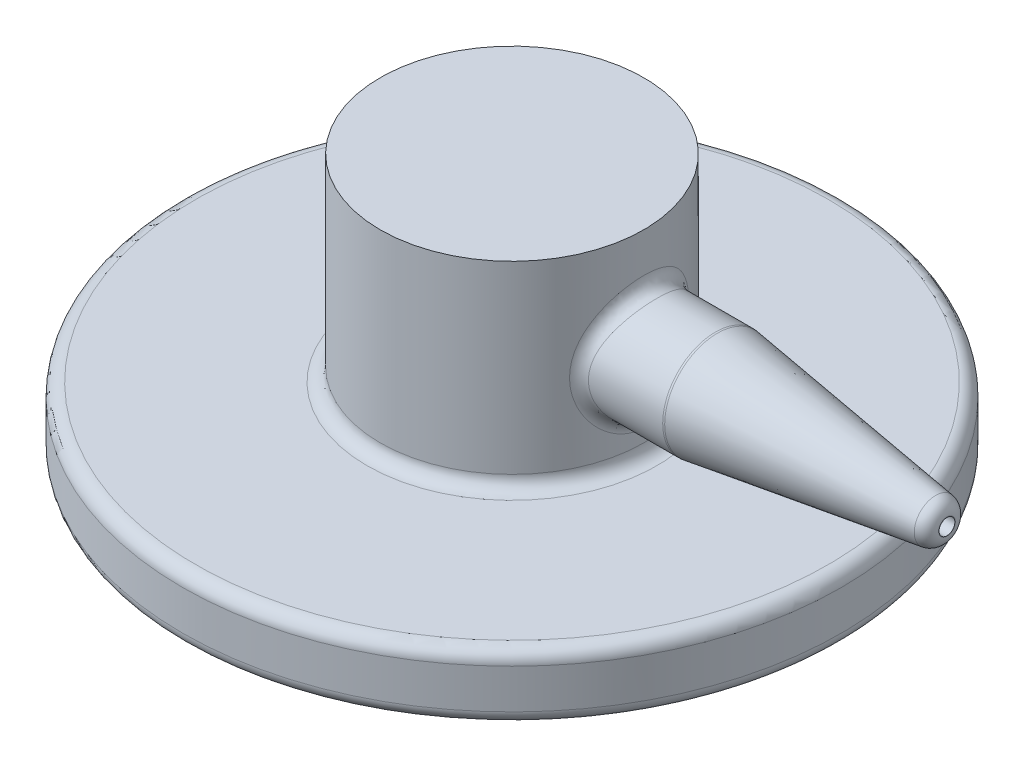
SolidWorks part; units mm, degrees
ref_plane "Ön Düzlem" through (0, 0, 0) normal (0, 0, 1) x (1, 0, 0)
ref_plane "Üst Düzlem" through (0, 0, 0) normal (0, 1, 0) x (1, 0, 0)
ref_plane "Sağ Düzlem" through (0, 0, 0) normal (1, 0, 0) x (0, 0, -1)
sketch "Sketch1" plane through (0, 0, 0) normal (0, 0, 1) x (1, 0, 0)
  line L0 (0, 20) -> (0, 0)
  line L8 (10, 20) -> (10, 5)
  line L9 (10, 5) -> (25, 5)
  line L10 (25, 5) -> (25, 0)
  line L11 (25, 0) -> (0, 0)
  line L13 (0, 20) -> (10, 20)
  dimension "D1" = 10
  dimension "D2" = 5
  dimension "D3" = 25
  dimension "D4" = 20
revolve "Revolve1" add sketch "Sketch1" angle 360 about L0
sketch "Sketch3" plane through (0, 0, 0) normal (1, 0, 0) x (0, 0, -1)
  line L0 (0, 0) -> (0, 64.7736) construction
  line L1 (-25, 0) -> (25, 0) construction
  circle A0 centre (0, 12) radius 4
  circle A1 centre (0, 12) radius 3
  dimension "D1" = 6
  dimension "D2" = 8
  dimension "D3" = 12
extrude "Boss-Extrude1" add sketch "Sketch3" along normal blind 25 contours A0
extrude "Boss-Extrude2" add sketch "Sketch3<5>" along normal blind 8 from surface contours A1 starting at face at (25, 12, -4)
sketch "Sketch3<5>" plane through (0, 0, 0) normal (1, 0, 0) x (0, 0, -1) same geometry as "Sketch3"
fillet "Fillet1" radius 1 2 edges at (0, 0, 25) (0, 5, 25)
sketch "Sketch11" plane through (0, 0, 0) normal (0, 0, 1) x (1, 0, 0)
  line L0 (0, 4) -> (0, 0)
  line L1 (0, 0) -> (22.0729, 0)
  line L2 (-24, 0) -> (24, 0) construction
  line L4 (0, 0) -> (0, 4.7847) construction
  arc A0 (0, 4) -> (22.0729, 0) centre (0.0014, -58.8935) cw
  dimension "D1" = 4
revolve "Cut-Revolve10" cut sketch "Sketch11" angle 360 about L4
sketch "Sketch15" plane through (0, 0, 0) normal (0, 1, 0) x (1, 0, 0)
  circle A0 centre (0, 0) radius 1.8
extrude "Cut-Extrude1" cut sketch "Sketch15" along normal blind 17 and the other way through all
sketch "Sketch16" plane through (0, 0, 0) normal (0, 0, 1) x (1, 0, 0)
  line L0 (33, 15) -> (33, 13.5)
  line L1 (33, 9) -> (33, 15) construction
  line L3 (25, 8) -> (25, 16) construction
  line L5 (33, 12) -> (25, 12) construction
  line L7 (25, 16) -> (10, 16) construction
  line L8 (15.5034, 16) -> (33, 13.5)
  line L9 (15.5034, 16) -> (33, 16)
  line L10 (33, 16) -> (33, 15)
revolve "Cut-Revolve12" cut sketch "Sketch16" angle 360 about L5
sketch "Sketch17" plane through (0, 0, 0) normal (0, 0, 1) x (1, 0, 0)
  line L1 (33, 12.6) -> (33, 12)
  line L4 (33, 12) -> (0, 12)
  line L10 (15.5034, 16) -> (15.5034, 14.8) construction
  line L11 (15.5034, 16) -> (15.5034, 8) construction
  line L13 (15.5034, 14.8) -> (0, 14.8)
  line L14 (0, 14.8) -> (0, 12)
  line L15 (15.5034, 14.8) -> (30.9004, 12.6)
  line L18 (33, 12.6) -> (30.9004, 12.6)
  dimension "D1" = 30.9004
  dimension "D2" = 12.6
  dimension "D3" = 14.8
  dimension "D4" = 33
  dimension "D5" = 12
revolve "Cut-Revolve13" cut sketch "Sketch17" angle 360 about L4
fillet "Fillet3" radius 1 4 edges at (33, 12, -1.5) (15.5034, 12, -4) (9.184, 12.5886, -3.9565) (0, 5, 10)
